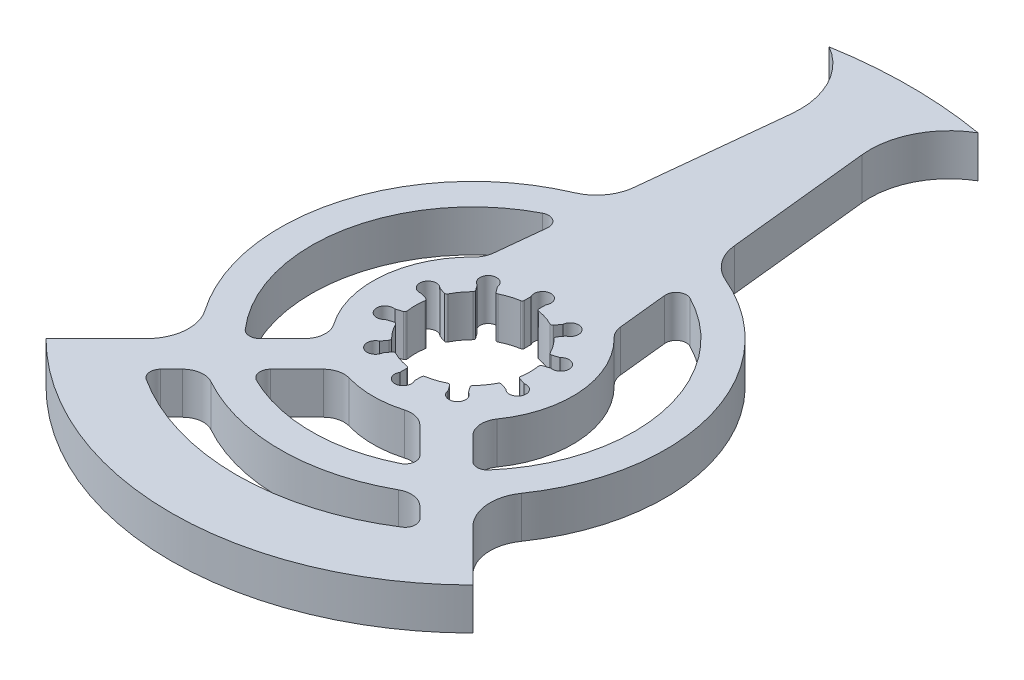
SolidWorks part; units mm, degrees
material "AISI Type A2 Tool Steel"
ref_plane "Front Plane" through (0, 0, 0) normal (0, 0, 1) x (1, 0, 0)
ref_plane "Top Plane" through (0, 0, 0) normal (0, 1, 0) x (1, 0, 0)
ref_plane "Right Plane" through (0, 0, 0) normal (1, 0, 0) x (0, 0, -1)
other "Center of Mass"
other "Bounding Box"
ref_plane "Default Plane" through (0, 2.286, 19.05) normal (0, -1, 0) x (-1, 0, 0)
sketch "Sketch1" plane through (0, 0, 0) normal (0, 1, 0) x (1, 0, 0)
  circle A0 centre (0, 0) radius 133.35 construction
  circle A1 centre (0, 0) radius 30.48
  circle A2 centre (0, 0) radius 17.4625
  dimension "D1" = 266.7
  dimension "D2" = 60.96
  dimension "D3" = 34.925
extrude "Boss-Extrude1" add sketch "Sketch1" along normal mid plane 12.7
sketch "Sketch2" plane through (0, 6.35, 0) normal (0, 1, 0) x (1, 0, 0)
  line L0 (-10.795, 107.95) -> (-19.6961, 23.2614)
  line L1 (19.6961, 23.2614) -> (10.795, 107.95)
  line L4 (0, 0) -> (0, 133.35) construction
  line L5 (-10.795, 107.95) -> (0, 107.95) construction
  line L6 (0, 107.95) -> (10.795, 107.95) construction
  line L7 (-22.6939, 131.4048) -> (0, 0) construction
  line L8 (-22.6939, 131.4048) -> (125.4677, 45.1673) construction
  circle A0 centre (0, 0) radius 133.35 construction
  circle A1 centre (0, 0) radius 133.35 construction
  arc A2 (-22.6939, 131.4048) -> (22.6939, 131.4048) centre (0, 0) cw
  arc A3 (-22.6939, 131.4048) -> (-10.795, 107.95) centre (-34.8727, 110.4807) cw
  circle A5 centre (0, 0) radius 30.48
  arc A6 (19.6961, 23.2614) -> (-19.6961, 23.2614) centre (0, 0) ccw
  arc A7 (-19.6961, 23.2614) -> (19.6961, 23.2614) centre (0, 0) ccw construction
  arc A8 (10.795, 107.95) -> (22.6939, 131.4048) centre (34.8727, 110.4807) cw
  dimension "D4" = 25.4
  dimension "D5" = 6
  dimension "D6" = 10.795
  dimension "D1" = 50
  dimension "D2" = 0
extrude "Boss-Extrude2" add sketch "Sketch2" against normal through all
sketch "Sketch3" plane through (0, 6.35, 0) normal (0, 1, 0) x (1, 0, 0)
  line L0 (-65.1069, -65.1069) -> (-21.5526, -21.5526)
  line L1 (21.5526, -21.5526) -> (65.1069, -65.1069)
  line L2 (0, -30.48) -> (0, -92.075) construction
  line L4 (-21.5526, -21.5526) -> (0, 0) construction
  line L5 (0, 0) -> (21.5526, -21.5526) construction
  arc A0 (-65.1069, -65.1069) -> (65.1069, -65.1069) centre (0, 0) ccw
  circle A1 centre (0, 0) radius 30.48 construction
  arc A3 (-21.5526, -21.5526) -> (21.5526, -21.5526) centre (0, 0) ccw
  point P13 (0, -92.075)
  dimension "D2" = 92.075
  dimension "D1" = 90
extrude "Boss-Extrude3" add sketch "Sketch3" against normal through all
sketch "Sketch5" plane through (0, 6.35, 0) normal (0, 1, 0) x (1, 0, 0)
  line L0 (0, 17.4625) -> (0, 21.2725) construction
  line L2 (-2.2225, 17.3205) -> (2.2225, 17.3205)
  line L3 (-2.2225, 17.3205) -> (-2.2225, 20.0168)
  line L5 (2.2225, 17.3205) -> (2.2225, 20.0168)
  arc A0 (2.2225, 20.0168) -> (-2.2225, 20.0168) centre (0, 21.2725) ccw
  circle A1 centre (0, 0) radius 17.4625 construction
  circle A2 centre (0, 21.2725) radius 4.5847 construction
  dimension "D2" = 5.1054
  dimension "D4" = 9.1694
  dimension "D1" = 3.81
  dimension "D3" = 4.445
extrude "Cut-Extrude2" cut sketch "Sketch5" against normal through all
pattern_circular "CirPattern1" count 10 over 360 about axis through (0, 6.35, 0) along (0, -1, 0) of "Cut-Extrude2"
sketch "Sketch6" plane through (0, 6.35, 0) normal (0, 1, 0) x (1, 0, 0)
  circle A0 centre (0, 0) radius 17.526
  arc A1 (-11.9788, 12.7062) -> (-15.786, 7.466) centre (0, 0) ccw construction
  dimension "D1" = 0.0635
extrude "Cut-Extrude3" cut sketch "Sketch6" against normal through all
sketch "Sketch7" plane through (0, 6.35, 0) normal (0, 1, 0) x (1, 0, 0)
  line L0 (-42.2449, -58.4093) -> (-11.8976, -28.062)
  line L1 (11.8976, -28.062) -> (42.2449, -58.4093)
  line L3 (-21.5526, -21.5526) -> (-65.1069, -65.1069) construction
  line L4 (65.1069, -65.1069) -> (21.5526, -21.5526) construction
  line L5 (-42.2449, -58.4093) -> (-50.3271, -50.3271) construction
  line L6 (42.2449, -58.4093) -> (50.3271, -50.3271) construction
  arc A0 (-11.8976, -28.062) -> (11.8976, -28.062) centre (0, 0) ccw
  arc A1 (-42.2449, -58.4093) -> (42.2449, -58.4093) centre (0, 0) ccw
  arc A2 (-65.1069, -65.1069) -> (65.1069, -65.1069) centre (0, 0) ccw construction
  arc A4 (21.5526, -21.5526) -> (19.6961, 23.2614) centre (0, 0) ccw construction
  dimension "D1" = 19.9898
  dimension "D2" = 11.43
extrude "Cut-Extrude4" cut sketch "Sketch7" against normal through all
sketch "Sketch8" plane through (0, 6.35, 0) normal (0, 1, 0) x (1, 0, 0)
  circle A0 centre (0, 0) radius 49.2125
  circle A1 centre (0, 0) radius 58.7375
  dimension "D1" = 9.525
  dimension "D2" = 117.475
extrude "Boss-Extrude4" add sketch "Sketch8" against normal through all
sketch "Sketch11" plane through (0, 6.35, 0) normal (0, 1, 0) x (1, 0, 0)
  line L0 (-7.5441, 29.5316) -> (-5.5081, 48.9033)
  line L1 (5.5081, 48.9033) -> (7.5441, 29.5316)
  line L3 (-17.2986, 46.072) -> (-19.6961, 23.2614) construction
  line L4 (19.6961, 23.2614) -> (17.2986, 46.072) construction
  line L5 (-6.5261, 39.2174) -> (-17.8935, 40.4122) construction
  line L6 (6.5261, 39.2174) -> (17.8935, 40.4122) construction
  arc A0 (-7.5441, 29.5316) -> (7.5441, 29.5316) centre (0, 0) cw
  arc A1 (-5.5081, 48.9033) -> (5.5081, 48.9033) centre (0, 0) cw
  arc A2 (-19.6961, 23.2614) -> (-21.5526, -21.5526) centre (0, 0) ccw construction
  arc A3 (-17.2986, 46.072) -> (-34.7985, -34.7985) centre (0, 0) ccw construction
  dimension "D1" = 11.43
extrude "Cut-Extrude6" [suppressed] cut sketch "Sketch11" against normal through all
fillet "Fillet1" radius 6.35 8 edges at (-21.5526, 0, 21.5526) (21.5526, 0, 21.5526) (19.6961, 0, -23.2614) (-19.6961, 0, -23.2614) (11.8976, 0, 28.062) (-11.8976, 0, 28.062) (32.6575, 0, 48.8219) (-32.6575, 0, 48.8219)
fillet "Fillet6" radius 0.635 20 edges at (-12.0164, 0, -12.758) (-15.8469, 0, -7.4858) (-17.2204, 0, -3.2584) (-17.2204, 0, 3.2584) (-15.8469, 0, 7.4858) (-12.0164, 0, 12.758) (-8.4203, 0, 15.3707) (-2.2225, 0, 17.3845) (2.2225, 0, 17.3845) (8.4203, 0, 15.3707) (12.0164, 0, 12.758) (15.8469, 0, 7.4858) (17.2204, 0, 3.2584) (17.2204, 0, -3.2584) (15.8469, 0, -7.4858) (12.0164, 0, -12.758) (8.4203, 0, -15.3707) (2.2225, 0, -17.3845) (-2.2225, 0, -17.3845) (-8.4203, 0, -15.3707)
fillet "Fillet7" radius 3.175 8 edges at (-25.7647, 0, 41.9291) (25.7647, 0, 41.9291) (34.7985, 0, 34.7985) (-34.7985, 0, 34.7985) (-17.2986, 0, -46.072) (17.2986, 0, -46.072) (42.2449, 0, 58.4093) (-42.2449, 0, 58.4093)
fillet "Fillet8" radius 12.7 4 edges at (-16.2071, 0, -56.4573) (16.2071, 0, -56.4573) (41.5337, 0, 41.5337) (-41.5337, 0, 41.5337)
fillet "Fillet9" [suppressed] radius 3.175
sketch "Sketch12" plane through (0, -6.35, 0) normal (0, -1, 0) x (1, 0, 0)
  line L0 (-58.7375, 0) -> (-53.975, 0) construction
  line L1 (-53.975, 0) -> (-49.2125, 0) construction
  circle A0 centre (0, 0) radius 53.975
  arc A1 (-48.2558, 33.4883) -> (-23.0251, -54.0365) centre (0, 0) ccw construction
  arc A2 (-37.1155, 32.3157) -> (-22.4793, -43.7784) centre (0, 0) ccw construction
equation "\"Unit Measure\"= \"BoundingVolume\" / \"Thickness\"'in^2"
